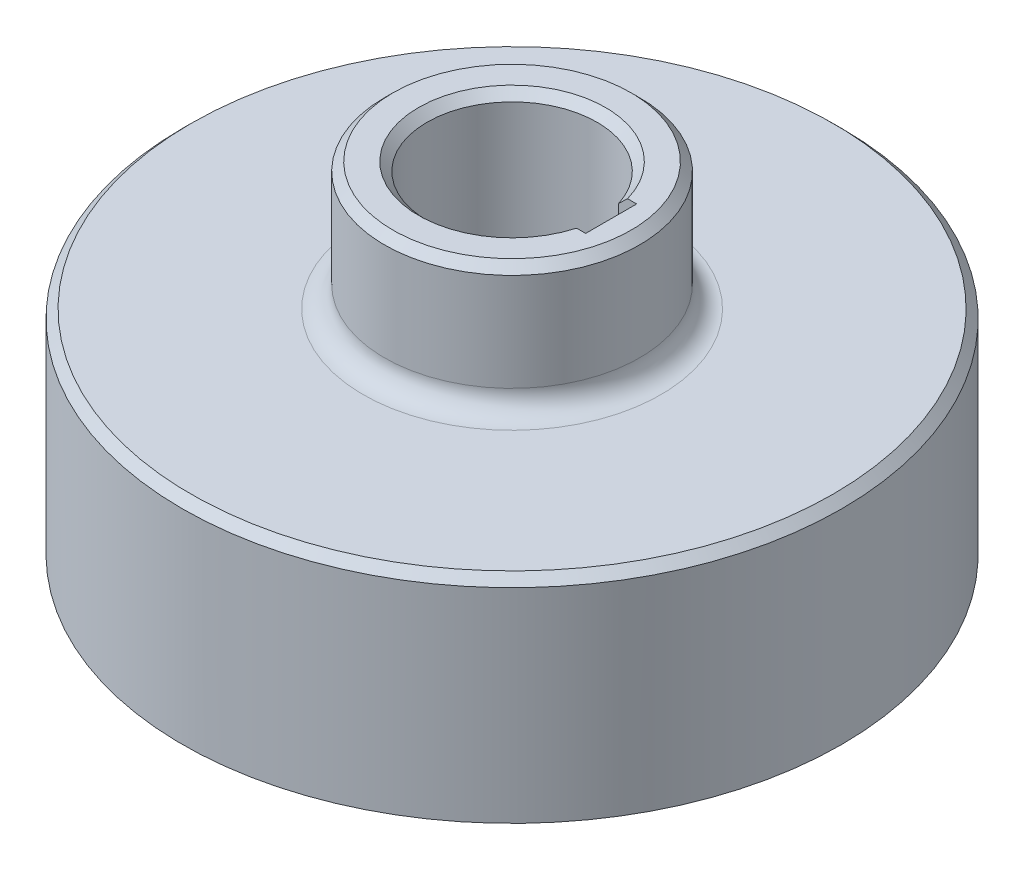
SolidWorks part; units mm, degrees
other "Markup1"
sketch "Sketch7" plane through (-77.5, 0, -77.5) normal (-0.5198, -0.8294, -0.2047) x (0.8494, -0.5274, -0.0202)
material "0.7060 (EN-GJS-600-3)"
ref_plane "Front Plane" through (0, 0, 0) normal (0, 0, 1) x (1, 0, 0)
ref_plane "Top Plane" through (0, 0, 0) normal (0, 1, 0) x (1, 0, 0)
ref_plane "Right Plane" through (0, 0, 0) normal (1, 0, 0) x (0, 0, -1)
sketch "Sketch1" plane through (0, 0, 0) normal (0, 0, 1) x (1, 0, 0)
  line L0 (0, -1292.3904) -> (0, 63327.1275) construction
  line L1 (20, 80) -> (30, 80)
  line L2 (30, 80) -> (30, 50)
  line L3 (30, 50) -> (77.5, 50)
  line L4 (77.5, 50) -> (77.5, 0)
  line L5 (77.5, 0) -> (63, 0)
  line L7 (70, 40) -> (25, 40)
  line L8 (20, 45) -> (20, 80)
  line L9 (70, 40) -> (70, 35)
  line L10 (63, 0) -> (63, 35)
  line L11 (63, 35) -> (70, 35)
  line L12 (25, 40) -> (25, 45)
  line L13 (25, 45) -> (20, 45)
  dimension "D1" = 40
  dimension "D2" = 5
  dimension "D3" = 5
  dimension "D4" = 155
  dimension "D5" = 10
  dimension "D6" = 60
  dimension "D7" = 126
  dimension "D8" = 140
  dimension "D9" = 35
  dimension "D10" = 40
  dimension "D11" = 5
revolve "Revolve1" add sketch "Sketch1" angle 360 about L0
fillet "Fillet1" radius 1.5 1 edges at (70, 40, 0)
sketch "Sketch2" plane through (0, 0, 0) normal (0, -1, 0) x (1, 0, 0)
  line L0 (0, -1000) -> (0, 49000) construction
  line L1 (-6.125, 68.8) -> (6.125, 68.8)
  line L2 (6.125, 68.8) -> (6.125, 62.7016)
  line L3 (-6.125, 68.8) -> (-6.125, 62.7016)
  circle A0 centre (0, 0) radius 63 construction
  arc A1 (6.125, 62.7016) -> (-6.125, 62.7016) centre (0, 0) ccw
  point P5 (0, 68.8)
  dimension "D1" = 12.25
  dimension "D2" = 68.8
extrude "Cut-Extrude1" cut sketch "Sketch2" against normal up to surface (35 mm away) up to face at (63, 35, 0)
fillet "Fillet2" radius 2 2 edges at (6.125, 17.5, 62.7016) (-6.125, 17.5, 62.7016)
pattern_circular "CirPattern1" count 6 over 360 about axis through (0, -1292.3904, 0) along (0, -1, 0) of "Cut-Extrude1", "Fillet2" reverse direction yes
fillet "Fillet3" radius 5 1 edges at (30, 50, 0)
chamfer "Chamfer1" distance 2 angle 45 3 edges at (30, 80, 0) (77.5, 50, 0) (20, 80, 0)
chamfer "Chamfer3" distance 1 angle 45 2 edges at (25, 40, 0) (20, 45, 0)
ref_plane "Plane1" through (23.3, 0, 0) normal (1, 0, 0) x (0, 0, -1)
sketch "Sketch3" plane through (23.3, 0, 0) normal (1, 0, 0) x (0, 0, -1)
  line L0 (28, 80) -> (-28, 80) construction
  line L1 (-6, 80) -> (6, 80)
  line L2 (-6, 80) -> (-6, 45)
  line L3 (-6, 45) -> (6, 45)
  line L4 (6, 80) -> (6, 45)
  line L6 (-21, 45) -> (21, 45) construction
  point P6 (0, 80)
  dimension "D1" = 12
extrude "Cut-Extrude2" cut sketch "Sketch3" against normal up to next
sketch "Sketch6" plane through (0, 0, 0) normal (0, 0, 1) x (1, 0, 0)
  line L0 (-70.25, -967.9081) -> (-70.25, 49032.0919) construction
  line L3 (-77.5, 0) -> (-63, 0) construction
  line L5 (-67.75, 0) -> (-67.75, 10)
  line L6 (-67.75, 10) -> (-70.25, 11.4434)
  line L7 (-70.25, 11.4434) -> (-70.25, 0)
  line L8 (-70.25, 0) -> (-67.75, 0)
  point P1 (-63, 0)
  point P11 (-70.25, 0)
  dimension "D1" = 60
  dimension "D2" = 5
  dimension "D3" = 10
revolve "Cut-Revolve1" cut sketch "Sketch6" angle 360 about L0
chamfer "Chamfer4" distance 0.5 angle 45 1 edges at (-70.25, 0, -2.5)
pattern_circular "CirPattern2" count 6 over 360 about axis through (0, -1292.3904, 0) along (0, -1, 0) of "Cut-Revolve1", "Chamfer4"
